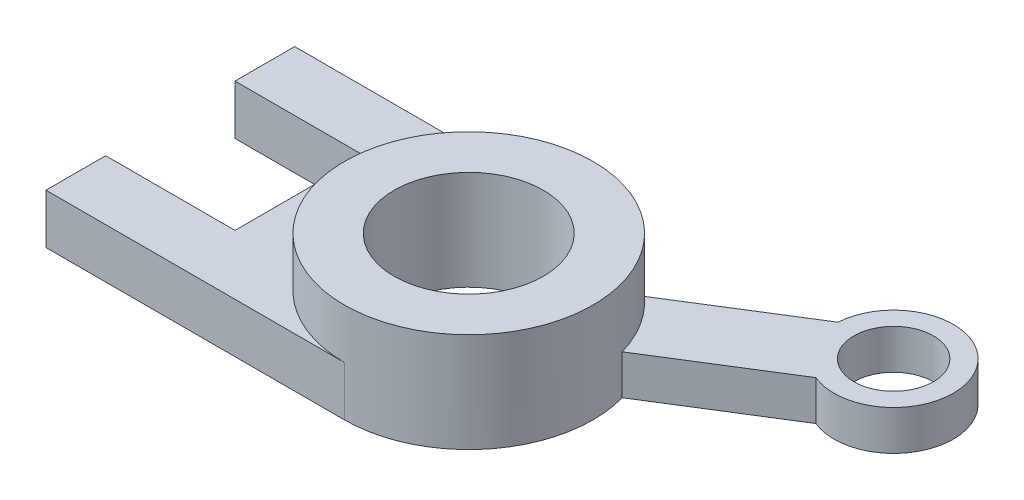
SolidWorks part; units mm, degrees
ref_plane "前视基准面" through (0, 0, 0) normal (0, 0, 1) x (1, 0, 0)
ref_plane "上视基准面" through (0, 0, 0) normal (0, 1, 0) x (1, 0, 0)
ref_plane "右视基准面" through (0, 0, 0) normal (1, 0, 0) x (0, 0, -1)
other "Configuration Table"
sketch "草图1" plane through (0, 0, 0) normal (0, 1, 0) x (1, 0, 0)
  line L0 (0, 0) -> (26.2895, 16.4275) construction
  line L1 (8.3219, 9.3272) -> (20.3019, 16.8132)
  line L2 (12.0313, 3.3909) -> (24.0113, 10.8768)
  line L3 (0, 12.5) -> (-30, 12.5)
  line L4 (-30, 12.5) -> (-30, 6.5)
  line L5 (-30, 6.5) -> (-17, 6.5)
  line L6 (-17, 6.5) -> (-17, -6.5)
  line L7 (0, 0) -> (33.7537, 0) construction
  line L8 (-30, -6.5) -> (-17, -6.5)
  line L9 (-30, -12.5) -> (-30, -6.5)
  line L10 (0, -12.5) -> (-30, -12.5)
  circle A0 centre (0, 0) radius 7.5
  circle A1 centre (0, 0) radius 12.5
  circle A2 centre (26.2895, 16.4275) radius 4
  circle A3 centre (26.2895, 16.4275) radius 6
  dimension "D1" = 15
  dimension "D2" = 25
  dimension "D4" = 8
  dimension "D5" = 12
  dimension "D3" = 31
  dimension "D6" = 7
  dimension "D7" = 13
  dimension "D8" = 25
  dimension "D9" = 30
  dimension "D10" = 32
  dimension "D11" = 13
extrude "凸台-拉伸1" add sketch "草图1" along normal blind 10 contours A1 A0 region at (10.3008, 0, -6.4366)
extrude "凸台-拉伸3" add sketch "草图1<4>" along normal blind 5 contours A1 L3 L4 L5 L6 L8 L9 L10 region at (-12.8905, 0, 0)
sketch "草图1<4>" plane through (0, 0, 0) normal (0, 1, 0) x (1, 0, 0) same geometry as "草图1"
extrude "凸台-拉伸4" add sketch "草图1<5>" along normal blind 4 contours A3 L1 A1 L2 | A3 A2 region at (15.9864, 0, -9.9894) region at (26.477, 0, -22.2548)
sketch "草图1<5>" plane through (0, 0, 0) normal (0, 1, 0) x (1, 0, 0) same geometry as "草图1"
